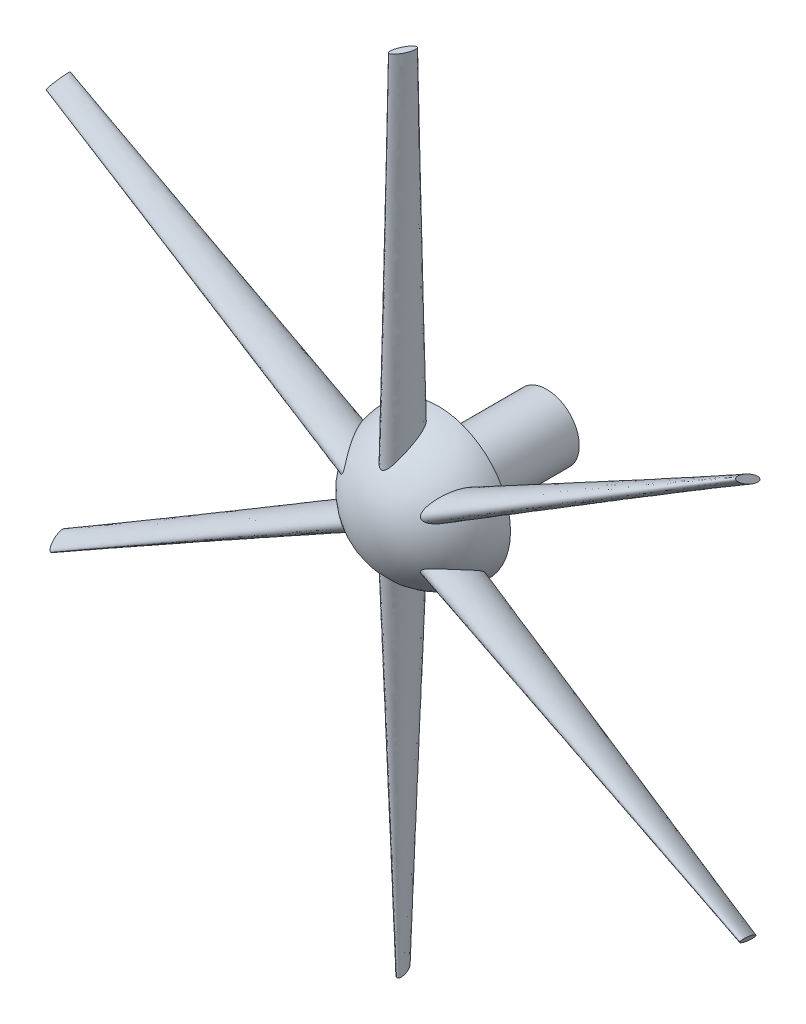
SolidWorks part; units mm, degrees
ref_plane "Front Plane" through (0, 0, 0) normal (0, 0, 1) x (1, 0, 0)
ref_plane "Top Plane" through (0, 0, 0) normal (0, 1, 0) x (1, 0, 0)
ref_plane "Right Plane" through (0, 0, 0) normal (1, 0, 0) x (0, 0, -1)
sketch "Sketch1" plane through (0, 0, 0) normal (0, 0, 1) x (1, 0, 0)
  circle A0 centre (0, 0) radius 5.715
  dimension "D1" = 11.43
extrude "Boss-Extrude1" add sketch "Sketch1" along normal blind 19.05
sketch "Sketch2" plane through (0, 0, 19.05) normal (0, 0, 1) x (1, 0, 0)
  circle A2 centre (0, 0) radius 12.7
  circle A3 centre (0, 0) radius 12.7
  dimension "D1" = 6.985
sketch "Sketch3" plane through (0, 0, 19.05) normal (0, 0, 1) x (1, 0, 0)
  line L0 (0, 12.7) -> (0, -12.7)
  circle A0 centre (0, 0) radius 12.7 construction
  arc A1 (0, 12.7) -> (0, -12.7) centre (0, 0) ccw
revolve "Revolve2" add sketch "Sketch3" angle 180 about L0 reverse direction yes
ref_plane "Plane1" through (0, 6.35, 0) normal (0, 1, 0) x (1, 0, 0)
sketch "Sketch5" plane through (0, 6.35, 0) normal (0, 1, 0) x (1, 0, 0)
  line L0 (0, -19.05) -> (0, -31.3685) construction
  line L1 (-12.7, -19.05) -> (12.7, -19.05) construction
  line L2 (0, -25.2093) -> (6.733, -25.2093) construction
  line L3 (0, -25.2093) -> (-6.7677, -25.2093) construction
  ellipse E0 centre (0, -25.2093) end of major axis (0, -29.0193) minor radius 1.905
  dimension "D1" = 1.905
  dimension "D2" = 7.62
ref_plane "Plane2" through (0, 69.85, 0) normal (0, 1, 0) x (1, 0, 0)
sketch "Sketch6" plane through (0, 69.85, 0) normal (0, 1, 0) x (1, 0, 0)
  line L0 (-6.7677, -25.2093) -> (6.733, -25.2093) construction
  line L1 (0, -19.05) -> (0, -31.3685) construction
  line L2 (-2.3377, -30.2224) -> (1.8308, -21.2832) construction
  ellipse E0 centre (0, -25.2093) end of major axis (-0.8051, -26.9358) minor radius 0.635
  dimension "D1" = 65
  dimension "D2" = 3.81
  dimension "D3" = 0.635
loft "Loft2" add profiles "Sketch5", "Sketch6" connector at (0, 6.35, 21.3993) connector at (0.8051, 69.85, 23.4827)
ref_axis "Axis1" through (0, 0, 63.8422) along (0, 0, -1)
pattern_circular "CirPattern1" count 6 over 360 about axis through (0, 0, 63.8422) along (0, 0, -1) of "Loft2"
